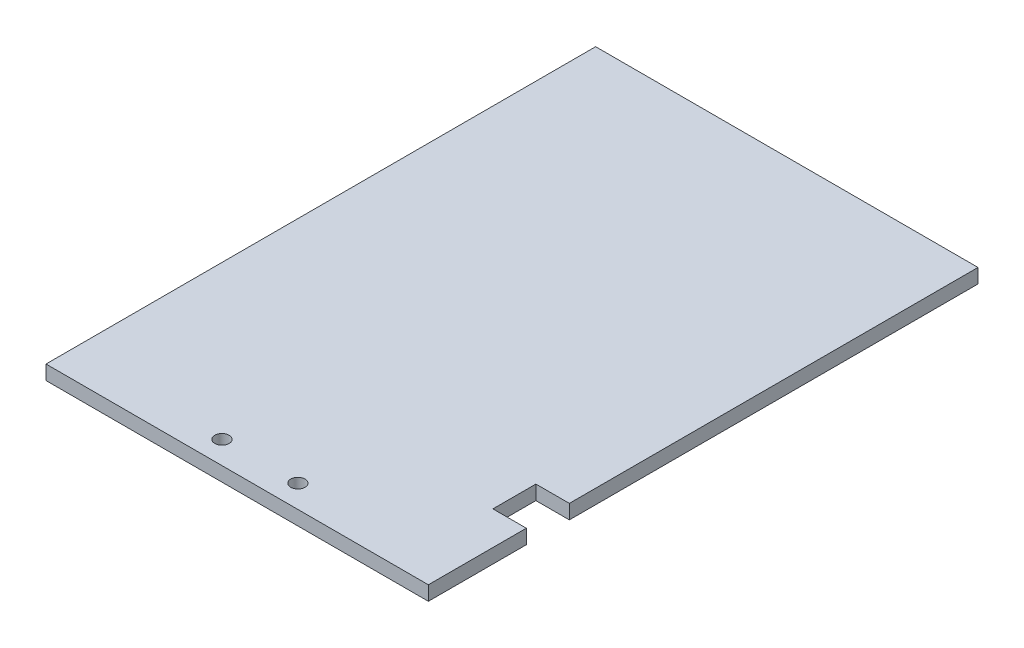
SolidWorks part; units mm, degrees
material "Acrilico TEC"
ref_plane "Front Plane" through (0, 0, 0) normal (0, 0, 1) x (1, 0, 0)
ref_plane "Top Plane" through (0, 0, 0) normal (0, 1, 0) x (1, 0, 0)
ref_plane "Right Plane" through (0, 0, 0) normal (1, 0, 0) x (0, 0, -1)
sketch "Sketch1" plane through (0, 0, 0) normal (0, 1, 0) x (1, 0, 0)
  line L1 (0, 0) -> (80, 0)
  line L2 (0, 0) -> (0, 105)
  line L3 (0, 105) -> (80, 105)
  line L4 (80, 0) -> (80, 105)
  dimension "D1" = 80
  dimension "D2" = 105
extrude "Boss-Extrude1" add sketch "Sketch1" along normal blind 3
sketch "Sketch4" plane through (0, 0, 0) normal (0, 0, 1) x (1, 0, 0)
  line L1 (0, 0) -> (80, 0)
  line L2 (0, 0) -> (0, 3)
  line L3 (0, 3) -> (80, 3)
  line L4 (80, 0) -> (80, 3)
extrude "Boss-Extrude3" add sketch "Sketch4" along normal blind 10
sketch "Sketch9" plane through (0, 3, 0) normal (0, 1, 0) x (1, 0, 0)
  line L0 (77, 15) -> (80, 15) construction
  line L1 (80, 19.5) -> (73, 19.5)
  line L2 (80, 19.5) -> (80, 10.5)
  line L3 (80, 10.5) -> (73, 10.5)
  line L4 (73, 19.5) -> (73, 10.5)
  line L5 (80, 19.5) -> (73, 10.5) construction
  line L6 (80, 10.5) -> (73, 19.5) construction
  line L8 (80, -10) -> (80, 105) construction
  dimension "D1" = 7
  dimension "D2" = 9
extrude "Cut-Extrude1" cut sketch "Sketch9" against normal blind 10
sketch "Croquis1" plane through (0, 3, 0) normal (0, 1, 0) x (1, 0, 0)
  line L0 (40, -10) -> (40, -5.24) construction
  line L1 (80, -10) -> (0, -10) construction
  line L2 (40, -5.24) -> (40, 105) construction
  line L3 (80, 105) -> (0, 105) construction
  circle A0 centre (32.06, -5.24) radius 1.5
  circle A1 centre (47.94, -5.24) radius 1.5
  dimension "D2" = 3
  dimension "D1" = 4.76
  dimension "D3" = 7.94
extrude "Cortar-Extruir1" cut sketch "Croquis1" against normal blind 10
